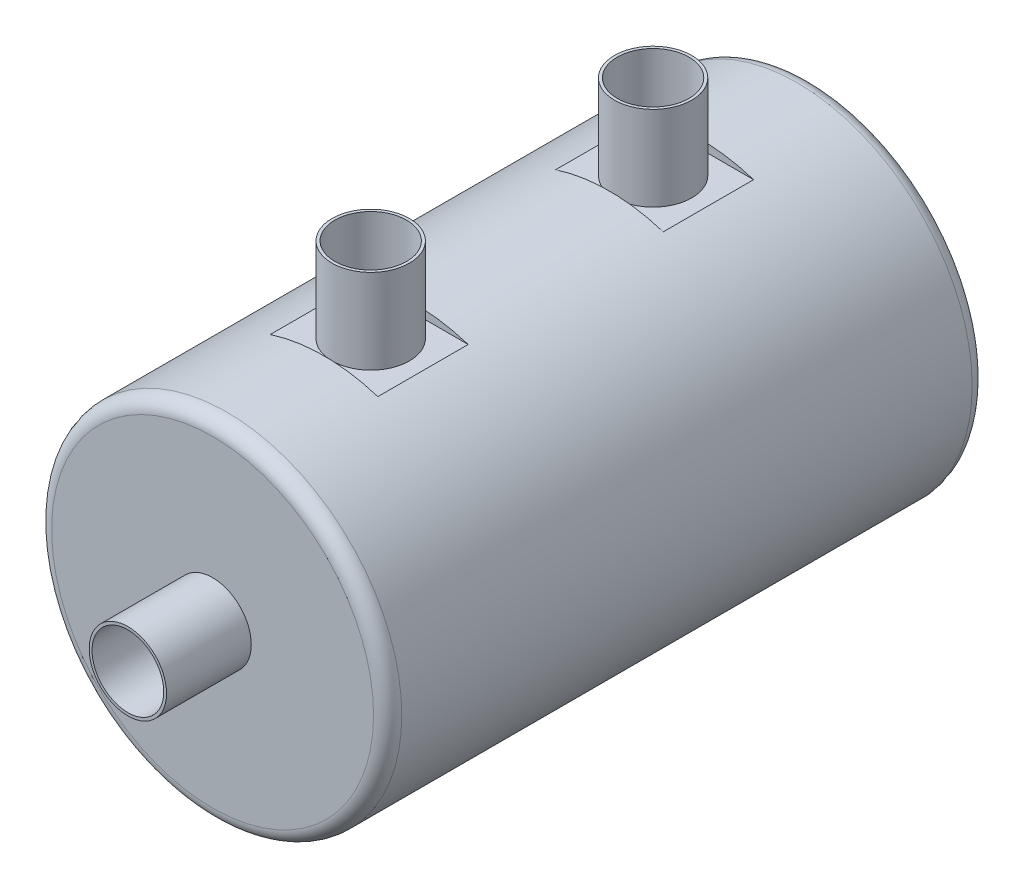
SolidWorks part; units mm, degrees
ref_plane "Front Plane" through (0, 0, 0) normal (0, 0, 1) x (1, 0, 0)
ref_plane "Top Plane" through (0, 0, 0) normal (0, 1, 0) x (1, 0, 0)
ref_plane "Right Plane" through (0, 0, 0) normal (1, 0, 0) x (0, 0, -1)
sketch "Sketch2" plane through (0, 0, 0) normal (0, 0, 1) x (1, 0, 0)
  circle A0 centre (0, 0) radius 28
  circle A1 centre (0, 0) radius 31
  dimension "D1" = 56
  dimension "D2" = 3
extrude "Boss-Extrude1" add sketch "Sketch2" against normal blind 100
sketch "Sketch3" plane through (0, 0, 0) normal (0, 0, 1) x (1, 0, 0)
  circle A0 centre (0, 0) radius 31 construction
  circle A1 centre (0, 0) radius 31
extrude "Boss-Extrude2" add sketch "Sketch3" along normal blind 3
sketch "Sketch4" plane through (0, 0, -100) normal (0, 0, -1) x (-1, 0, 0)
  circle A0 centre (0, 0) radius 31 construction
  circle A1 centre (0, 0) radius 31
extrude "Boss-Extrude3" add sketch "Sketch4" along normal blind 3
sketch "Sketch5" plane through (0, 0, 0) normal (1, 0, 0) x (0, 0, -1)
  line L0 (103, 31) -> (-3, 31) construction
  line L1 (103, 31) -> (-3, 31)
  line L2 (50, 43.499) -> (50, -24.284) construction
  line L3 (16.7301, 29.5) -> (32.7301, 31) construction
  line L4 (83.2699, 31) -> (67.2699, 31)
  line L5 (83.2699, 31) -> (83.2699, 29.5)
  line L6 (83.2699, 29.5) -> (67.2699, 29.5)
  line L7 (67.2699, 31) -> (67.2699, 29.5)
  line L8 (83.2699, 31) -> (67.2699, 29.5) construction
  line L9 (83.2699, 29.5) -> (67.2699, 31) construction
  line L10 (16.7301, 31) -> (32.7301, 29.5) construction
  line L11 (32.7301, 31) -> (32.7301, 29.5)
  line L12 (16.7301, 29.5) -> (32.7301, 29.5)
  line L13 (16.7301, 31) -> (16.7301, 29.5)
  line L14 (16.7301, 31) -> (32.7301, 31)
  point P2 (50, 31)
  point P9 (75.2699, 30.25)
  point P15 (24.7301, 30.25)
  dimension "D1" = 16
  dimension "D2" = 1.5
  dimension "D3" = 67.2699
extrude "Cut-Extrude1" cut sketch "Sketch5" against normal through all and the other way through all contours L1 L7 L6 L5 | L1 L13 L12 L11 region at (0, 30.25, -75.2699) region at (0, 30.25, -24.7301)
sketch "Sketch6" plane through (0, 29.5, 0) normal (0, 1, 0) x (1, 0, 0)
  line L0 (-31, -3) -> (31, -3) construction
  line L1 (31, 103) -> (-31, 103) construction
  circle A0 centre (0, 25) radius 6.35
  circle A1 centre (0, 75) radius 6.35
  circle A2 centre (0, 25) radius 6.85
  circle A3 centre (0, 75) radius 6.85
  point P8 (0, 0)
  dimension "D1" = 12.7
  dimension "D2" = 12.7
  dimension "D5" = 28
  dimension "D6" = 28
  dimension "D3" = 0.5
  dimension "D4" = 0.5
extrude "Boss-Extrude4" add sketch "Sketch6" along normal blind 15
extrude "Cut-Extrude2" cut sketch "Sketch6<2>" against normal blind 15 contours A0 | A1 region at (0, 29.5, -25) region at (0, 29.5, -75)
sketch "Sketch6<2>" plane through (0, 29.5, 0) normal (0, 1, 0) x (1, 0, 0) same geometry as "Sketch6"
sketch "Sketch7" plane through (0, 0, 3) normal (0, 0, 1) x (1, 0, 0)
  circle A0 centre (0, 0) radius 6.35
  circle A1 centre (0, 0) radius 6.85
  dimension "D1" = 12.7
  dimension "D2" = 0.5
extrude "Boss-Extrude5" add sketch "Sketch7" along normal blind 15
ref_plane "Plane1" through (0, 0, -50) normal (0, 0, 1) x (1, 0, 0)
extrude "Cut-Extrude3" cut sketch "Sketch7<2>" against normal blind 15 contours A0 region at (0, 0, 3)
sketch "Sketch7<2>" plane through (0, 0, 3) normal (0, 0, 1) x (1, 0, 0) same geometry as "Sketch7"
mirror "Mirror2" about plane through (0, 0, -50) normal (0, 0, 1) of "Cut-Extrude3", "Boss-Extrude5"
fillet "Fillet1" radius 2.5 2 edges at (-31, 0, -103) (31, 0, 3)
